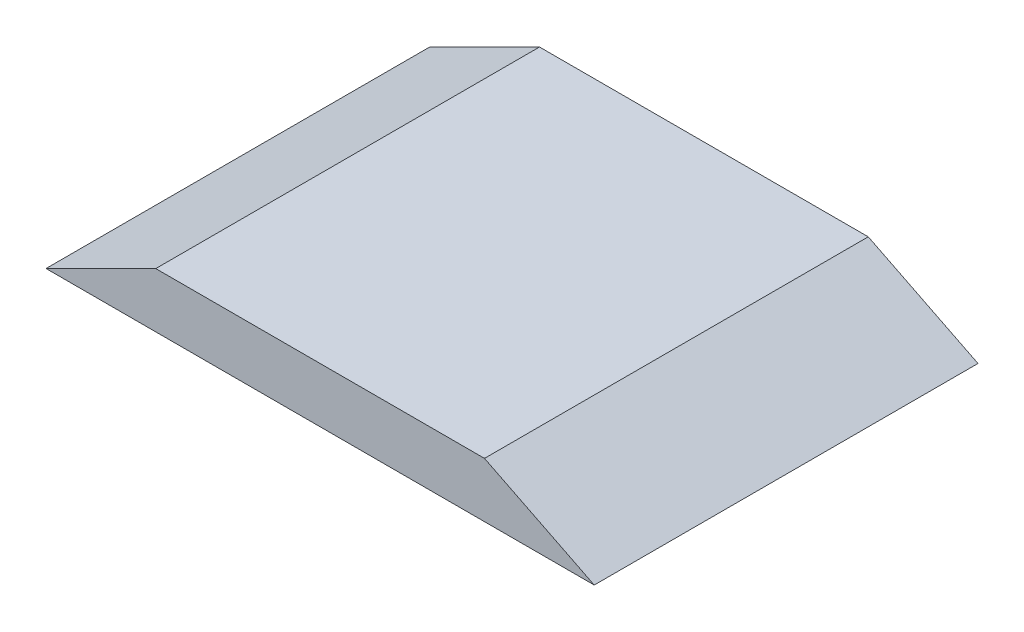
SolidWorks part; units mm, degrees
ref_plane "Front Plane" through (0, 0, 0) normal (0, 0, 1) x (1, 0, 0)
ref_plane "Top Plane" through (0, 0, 0) normal (0, 1, 0) x (1, 0, 0)
ref_plane "Right Plane" through (0, 0, 0) normal (1, 0, 0) x (0, 0, -1)
sketch "Sketch1" plane through (0, 0, 0) normal (0, 0, 1) x (1, 0, 0)
  line L0 (-63.5, -6.35) -> (-38.0767, 6.35)
  line L1 (63.5, -6.35) -> (-63.5, -6.35) construction
  line L2 (63.5, -6.35) -> (63.5, 6.35) construction
  line L3 (63.5, 6.35) -> (-63.5, 6.35) construction
  line L4 (-63.5, -6.35) -> (-63.5, 6.35) construction
  line L5 (63.5, -6.35) -> (-63.5, 6.35) construction
  line L6 (63.5, 6.35) -> (-63.5, -6.35) construction
  line L7 (-38.0767, 6.35) -> (38.0767, 6.35)
  line L8 (38.0767, 6.35) -> (63.5, -6.35)
  line L9 (63.5, -6.35) -> (-63.5, -6.35)
  point P0 (0, 0)
  point P6 (-42.8751, 6.35)
  point P9 (-38.0767, 6.35)
  dimension "D1" = 127
  dimension "D2" = 12.7
extrude "Boss-Extrude1" add sketch "Sketch1" along normal blind 88.9
